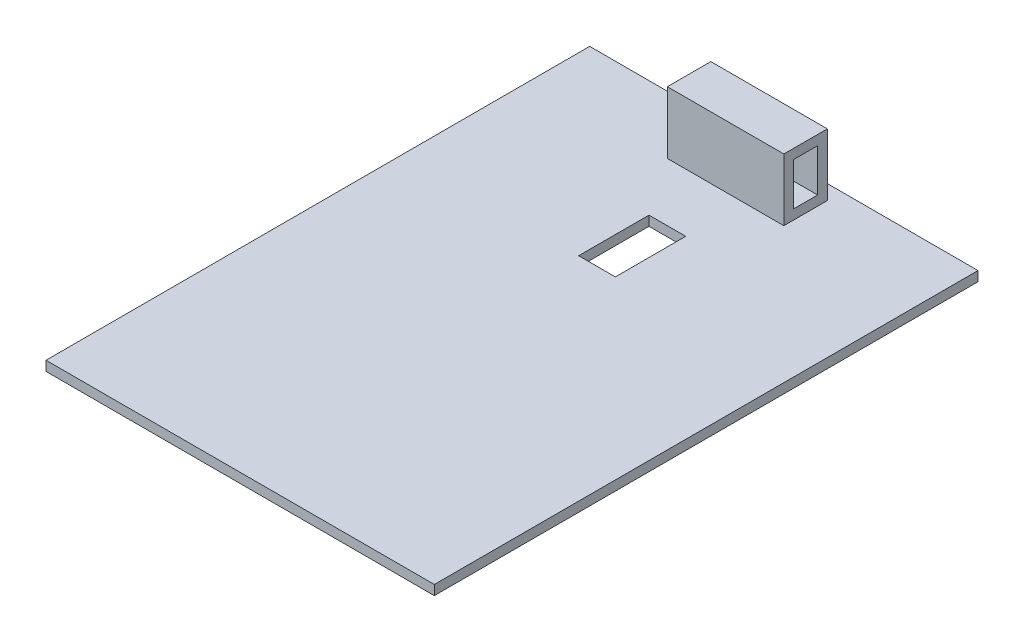
SolidWorks part; units mm, degrees
ref_plane "Front Plane" through (0, 0, 0) normal (0, 0, 1) x (1, 0, 0)
ref_plane "Top Plane" through (0, 0, 0) normal (0, 1, 0) x (1, 0, 0)
ref_plane "Right Plane" through (0, 0, 0) normal (1, 0, 0) x (0, 0, -1)
sketch "Sketch1" plane through (0, 0, 0) normal (0, 1, 0) x (1, 0, 0)
  line L0 (63.5, 177.8) -> (63.5, 0) construction
  line L1 (0, 0) -> (127, 0)
  line L2 (0, 0) -> (0, 177.8)
  line L3 (0, 177.8) -> (127, 177.8)
  line L4 (127, 0) -> (127, 177.8)
  line L5 (57.5, 139.7) -> (69.5, 139.7)
  line L6 (57.5, 139.7) -> (57.5, 116.7)
  line L7 (57.5, 116.7) -> (69.5, 116.7)
  line L8 (69.5, 139.7) -> (69.5, 116.7)
  line L9 (63.5, 139.7) -> (63.5, 116.7) construction
  dimension "D1" = 127
  dimension "D2" = 177.8
  dimension "D3" = 12
  dimension "D4" = 23
  dimension "D5" = 38.1
extrude "Boss-Extrude2" add sketch "Sketch1" along normal blind 3.175
ref_plane "Plane1" through (0, 0, -158.75) normal (0, 0, -1) x (-1, 0, 0)
sketch "Sketch5" plane through (0, 0, -158.75) normal (0, 0, -1) x (-1, 0, 0)
  line L0 (-127, 3.175) -> (0, 3.175) construction
  line L1 (-82.55, 23.495) -> (-44.45, 23.495)
  line L2 (-82.55, 23.495) -> (-82.55, 3.175)
  line L3 (-82.55, 3.175) -> (-44.45, 3.175)
  line L4 (-44.45, 23.495) -> (-44.45, 3.175)
  line L5 (-63.5, 23.495) -> (-63.5, 3.175) construction
  line L6 (-63.5, 3.175) -> (-63.5, 0) construction
  line L7 (-127, 0) -> (0, 0) construction
  dimension "D1" = 20.32
  dimension "D2" = 38.1
extrude "Boss-Extrude3" add sketch "Sketch5" along normal blind 14.224
sketch "Sketch8" plane through (82.55, 0, 0) normal (1, 0, 0) x (0, 0, -1)
  line L0 (172.974, 23.495) -> (172.974, 3.175) construction
  line L1 (161.925, 20.32) -> (169.799, 20.32)
  line L2 (161.925, 20.32) -> (161.925, 6.35)
  line L3 (161.925, 6.35) -> (169.799, 6.35)
  line L4 (169.799, 20.32) -> (169.799, 6.35)
  line L5 (172.974, 23.495) -> (158.75, 23.495) construction
  line L9 (158.75, -22.942) -> (158.75, 22.942) construction
  line L10 (172.974, 3.175) -> (158.75, 3.175) construction
  dimension "D1" = 3.175
  dimension "D2" = 3.175
  dimension "D3" = 3.175
  dimension "D4" = 3.175
extrude "Cut-Extrude1" cut sketch "Sketch8" against normal up to next
